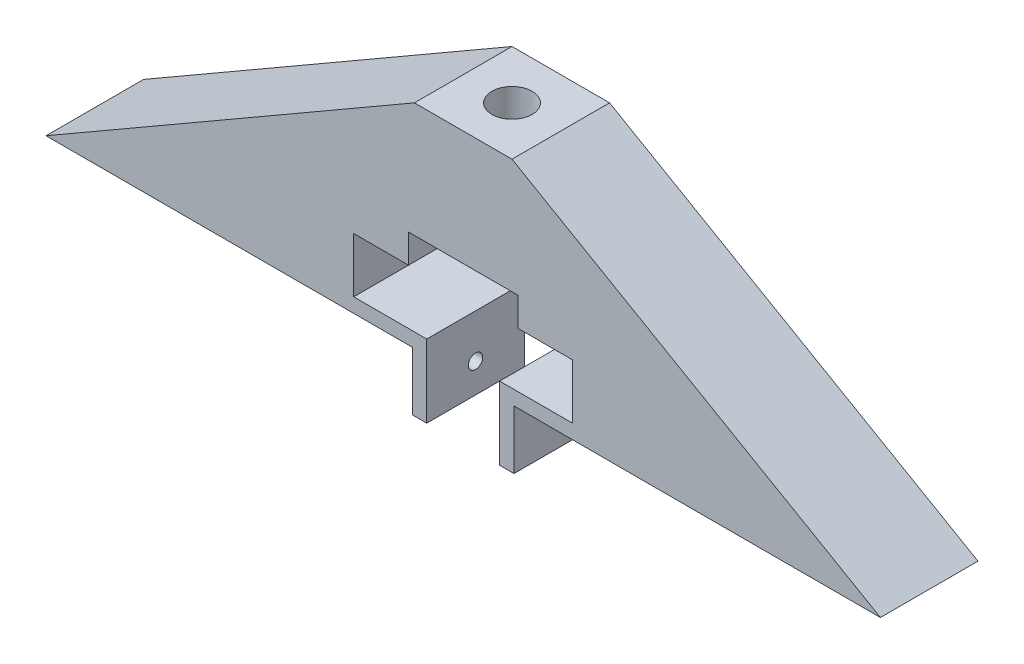
SolidWorks part; units mm, degrees
ref_plane "Front Plane" through (0, 0, 0) normal (0, 0, 1) x (1, 0, 0)
ref_plane "Top Plane" through (0, 0, 0) normal (0, 1, 0) x (1, 0, 0)
ref_plane "Right Plane" through (0, 0, 0) normal (1, 0, 0) x (0, 0, -1)
sketch "Sketch1" plane through (0, 0, 0) normal (0, 0, 1) x (1, 0, 0)
  line L0 (-145.345, 0) -> (-17.7, 0)
  line L1 (-17.7, 0) -> (-17.7, -20.4)
  line L2 (-17.7, -20.4) -> (-12.7, -20.4)
  line L3 (-12.7, -20.4) -> (-12.7, 5)
  line L4 (-12.7, 5) -> (-38.15, 5)
  line L5 (-38.15, 5) -> (-38.15, 24.1)
  line L6 (-38.15, 24.1) -> (-19.05, 24.1)
  line L7 (38.15, 24.1) -> (38.15, 5)
  line L8 (38.15, 5) -> (12.7, 5)
  line L9 (12.7, 5) -> (12.7, -20.4)
  line L10 (12.7, -20.4) -> (17.7, -20.4)
  line L11 (17.7, -20.4) -> (17.7, 0)
  line L12 (17.7, 0) -> (145.345, 0)
  line L13 (145.345, 0) -> (17, 74.1)
  line L14 (17, 74.1) -> (-17, 74.1)
  line L15 (-17, 74.1) -> (-145.345, 0)
  line L16 (-19.05, 24.1) -> (-19.05, 34.1)
  line L17 (-19.05, 34.1) -> (19.05, 34.1)
  line L18 (19.05, 34.1) -> (19.05, 24.1)
  line L19 (19.05, 24.1) -> (38.15, 24.1)
  point P18 (0, 74.1)
  point P22 (0, 34.1)
  dimension "D1" = 30
  dimension "D2" = 10
  dimension "D3" = 34
  dimension "D4" = 25.4
  dimension "D5" = 76.3
  dimension "D6" = 19.1
  dimension "D7" = 5
  dimension "D8" = 5
  dimension "D9" = 25.4
  dimension "D10" = 38.1
  dimension "D11" = 40
extrude "Boss-Extrude1" add sketch "Sketch1" along normal blind 34
sketch "Sketch2" plane through (0, 74.1, 0) normal (0, 1, 0) x (1, 0, 0)
  line L0 (-17, 0) -> (17, -34) construction
  line L1 (17, 0) -> (-17, -34) construction
  circle A0 centre (0, -17) radius 7
  dimension "D1" = 14
extrude "Cut-Extrude1" cut sketch "Sketch2" against normal blind 35
sketch "Sketch3" plane through (17.7, 0, 0) normal (1, 0, 0) x (0, 0, -1)
  line L0 (-34, 0) -> (0, -20.4) construction
  line L1 (0, 0) -> (-34, -20.4) construction
  circle A0 centre (-17, -10.2) radius 2.5
  dimension "D1" = 5
extrude "Cut-Extrude2" cut sketch "Sketch3" against normal through all
